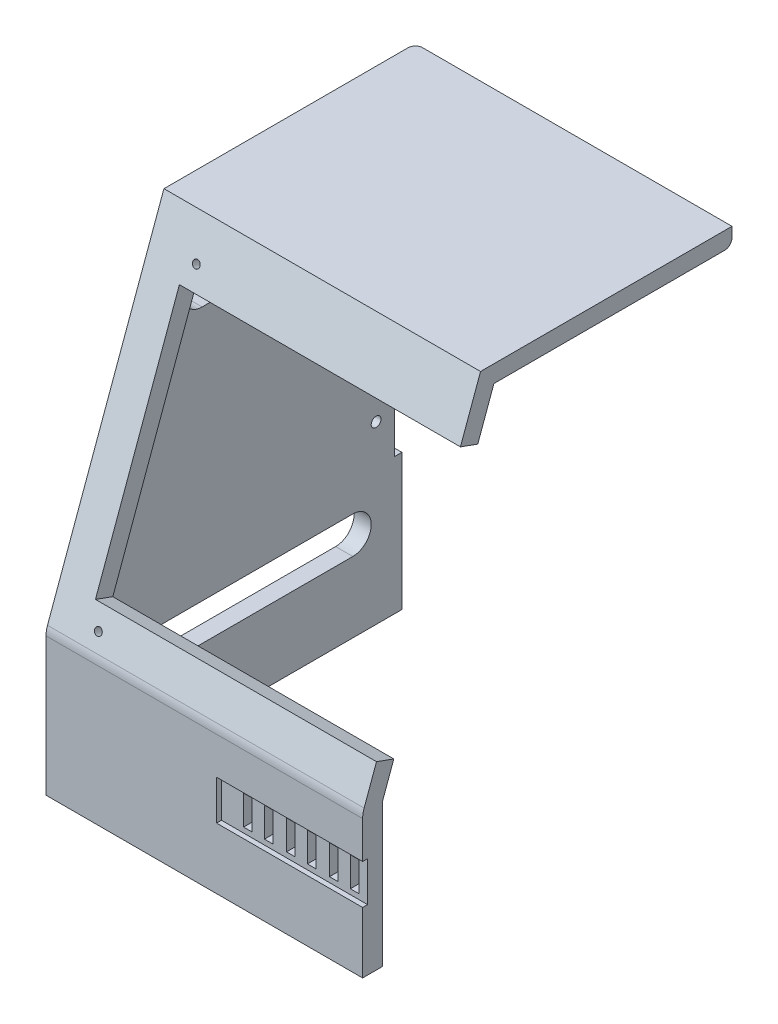
SolidWorks part; units mm, degrees
ref_plane "Front Plane" through (0, 0, 0) normal (0, 0, 1) x (1, 0, 0)
ref_plane "Top Plane" through (0, 0, 0) normal (0, 1, 0) x (1, 0, 0)
ref_plane "Right Plane" through (0, 0, 0) normal (1, 0, 0) x (0, 0, -1)
sketch "Sketch1" plane through (0, 0, 0) normal (0, 0, 1) x (1, 0, 0)
  line L0 (0, 0) -> (170, 0)
  line L1 (170, 0) -> (170, 130)
  line L2 (170, 130) -> (0, 130)
  line L3 (0, 130) -> (0, 0)
  dimension "D1" = 170
  dimension "D2" = 130
extrude "Boss-Extrude1" add sketch "Sketch1" along normal blind 8
sketch "Sketch2" plane through (0, 0, 8) normal (0, 0, 1) x (1, 0, 0)
  line L0 (85, 130) -> (85, 0) construction
  line L1 (170, 130) -> (0, 130) construction
  line L2 (0, 0) -> (170, 0) construction
  line L3 (0, 65) -> (170, 65) construction
  line L4 (0, 130) -> (0, 0) construction
  line L5 (170, 0) -> (170, 130) construction
  line L6 (6.55, 123.35) -> (163.45, 123.35) construction
  line L7 (163.45, 123.35) -> (163.45, 6.65) construction
  line L8 (163.45, 6.65) -> (6.55, 6.65) construction
  line L9 (6.55, 6.65) -> (6.55, 123.35) construction
  line L10 (2.5, 115) -> (167.5, 115)
  line L11 (2.5, 115) -> (2.5, 15)
  line L12 (2.5, 15) -> (167.5, 15)
  line L13 (167.5, 15) -> (167.5, 115)
  circle A0 centre (6.55, 123.35) radius 1.5
  circle A1 centre (163.45, 123.35) radius 1.5
  circle A2 centre (6.55, 6.65) radius 1.5
  circle A3 centre (163.45, 6.65) radius 1.5
  dimension "D3" = 165
  dimension "D1" = 156.9
  dimension "D2" = 116.7
  dimension "D4" = 100
extrude "Cut-Extrude1" cut sketch "Sketch2" against normal blind 21
sketch "Sketch3" plane through (0, 0, 8) normal (0, 0, 1) x (1, 0, 0)
  line L0 (0, 0) -> (170, 0)
  line L1 (170, 0) -> (170, -20)
  line L2 (170, -20) -> (0, -20)
  line L3 (0, -20) -> (0, 0)
extrude "Boss-Extrude2" add sketch "Sketch3" against normal blind 8
sketch "Sketch4" plane through (0, 0, 8) normal (0, 0, 1) x (1, 0, 0)
  line L0 (0, 0) -> (0, -20) construction
  line L1 (0, -10) -> (170, -10) construction
  line L2 (170, -20) -> (170, 130) construction
  line L3 (85, 15) -> (85, -20) construction
  line L4 (2.5, 15) -> (167.5, 15) construction
  line L5 (0, -20) -> (170, -20) construction
  line L6 (52.5, -1.9) -> (52.5, -18.1)
  line L7 (52.5, -1.9) -> (117.5, -1.9)
  line L8 (117.5, -1.9) -> (117.5, -18.1)
  line L9 (117.5, -18.1) -> (52.5, -18.1)
  dimension "D1" = 65
  dimension "D2" = 16.2
extrude "Cut-Extrude2" cut sketch "Sketch4" against normal blind 2
sketch "Sketch5" plane through (0, 0, 6) normal (0, 0, 1) x (1, 0, 0)
  line L0 (52.5, -10) -> (117.5, -10) construction
  line L1 (52.5, -1.9) -> (52.5, -18.1) construction
  line L2 (117.5, -18.1) -> (117.5, -1.9) construction
  line L3 (67.5, -1.9) -> (67.5, -18.1) construction
  line L4 (117.5, -1.9) -> (52.5, -1.9) construction
  line L5 (52.5, -18.1) -> (117.5, -18.1) construction
  line L6 (85, -1.9) -> (85, -18.1) construction
  line L7 (117.5, -1.9) -> (52.5, -1.9) construction
  line L8 (52.5, -18.1) -> (117.5, -18.1) construction
  line L9 (102.5, -1.9) -> (102.5, -18.1) construction
  line L10 (52.5, -1.9) -> (52.5, -18.1) construction
  line L11 (93.75, -1.9) -> (93.75, -18.1) construction
  line L12 (61.5, -4) -> (73.5, -4) construction
  line L13 (73.5, -4) -> (73.5, -16) construction
  line L14 (73.5, -16) -> (61.5, -16) construction
  line L15 (61.5, -16) -> (61.5, -4) construction
  line L16 (96.5, -16) -> (96.5, -4) construction
  line L17 (79, -4) -> (79, -16) construction
  line L18 (79, -16) -> (91, -16) construction
  line L19 (91, -16) -> (91, -4) construction
  line L20 (91, -4) -> (79, -4) construction
  line L21 (108.5, -16) -> (96.5, -16) construction
  line L22 (108.5, -4) -> (108.5, -16) construction
  line L23 (96.5, -4) -> (108.5, -4) construction
  line L24 (61.5, -4) -> (65, -4)
  line L25 (65, -4) -> (65, -16)
  line L26 (65, -16) -> (61.5, -16)
  line L27 (61.5, -16) -> (61.5, -4)
  line L28 (70, -16) -> (73.5, -16)
  line L29 (70, -4) -> (70, -16)
  line L30 (73.5, -4) -> (70, -4)
  line L31 (73.5, -16) -> (73.5, -4)
  line L32 (76.25, -1.9) -> (76.25, -18.1) construction
  line L33 (82.5, -4) -> (82.5, -16)
  line L34 (79, -4) -> (82.5, -4)
  line L35 (79, -16) -> (79, -4)
  line L36 (82.5, -16) -> (79, -16)
  line L37 (87.5, -16) -> (91, -16)
  line L38 (87.5, -4) -> (87.5, -16)
  line L39 (91, -4) -> (87.5, -4)
  line L40 (91, -16) -> (91, -4)
  line L41 (100, -4) -> (100, -16)
  line L42 (96.5, -4) -> (100, -4)
  line L43 (96.5, -16) -> (96.5, -4)
  line L44 (100, -16) -> (96.5, -16)
  line L45 (108.5, -4) -> (105, -4)
  line L46 (108.5, -16) -> (108.5, -4)
  line L47 (105, -16) -> (108.5, -16)
  line L48 (105, -4) -> (105, -16)
  dimension "D1" = 15
  dimension "D2" = 17.5
  dimension "D3" = 17.5
  dimension "D4" = 15
  dimension "D5" = 12
  dimension "D6" = 12
  dimension "D7" = 8.75
  dimension "D8" = 8.75
extrude "Cut-Extrude3" cut sketch "Sketch5" against normal blind 35
sketch "Sketch6" plane through (0, 0, 8) normal (0, 0, 1) x (1, 0, 0)
  line L0 (15.5044, 140) -> (225, 140)
  line L1 (225, 140) -> (225, -35)
  line L2 (225, -35) -> (-10, -35)
  line L3 (-10, -35) -> (-10, 140)
  line L4 (-10, 140) -> (15.5044, 140)
  line L5 (170, 130) -> (0, 130) construction
  line L6 (170, -20) -> (170, 130) construction
  line L7 (0, -20) -> (170, -20) construction
  line L8 (0, 130) -> (170, 130)
  line L9 (170, 130) -> (170, -20)
  line L10 (170, -20) -> (0, -20)
  line L11 (0, -20) -> (0, 130)
  dimension "D1" = 10
  dimension "D2" = 10
  dimension "D3" = 55
  dimension "D4" = 15
extrude "Boss-Extrude3" add sketch "Sketch6" against normal blind 8
sketch "Sketch7" plane through (0, 0, 8) normal (0, 0, 1) x (1, 0, 0)
  line L0 (-10, 140) -> (-17, 140)
  line L1 (-17, 140) -> (-17, -42)
  line L2 (-17, -42) -> (232, -42)
  line L3 (232, -42) -> (232, 140)
  line L4 (232, 140) -> (225, 140)
  line L5 (225, 140) -> (225, -35)
  line L6 (225, -35) -> (-10, -35)
  line L7 (-10, -35) -> (-10, 140)
  dimension "D1" = 7
  dimension "D2" = 7
  dimension "D3" = 7
extrude "Boss-Extrude4" add sketch "Sketch7" against normal blind 138
sketch "Sketch8" plane through (0, -42, 0) normal (0, -1, 0) x (1, 0, 0)
  line L0 (-17, 8) -> (-17, -130)
  line L1 (-17, -130) -> (232, -130)
  line L2 (232, -130) -> (232, 8)
  line L3 (232, 8) -> (-17, 8)
extrude "Boss-Extrude5" add sketch "Sketch8" along normal blind 1
sketch "Sketch9" plane through (232, 0, 0) normal (1, 0, 0) x (0, 0, -1)
  line L0 (75, 140) -> (75, -48) construction
  line L1 (130, 140) -> (-8, 140) construction
  line L3 (-8, -43) -> (-8, 140) construction
  line L4 (-8, 35) -> (130, 35) construction
  line L5 (130, -43) -> (130, 140) construction
  line L6 (38.6, 71.625) -> (111.4, 71.625)
  line L7 (111.4, 71.625) -> (111.4, -1.625)
  line L8 (111.4, -1.625) -> (38.6, -1.625)
  line L9 (38.6, -1.625) -> (38.6, 71.625)
  dimension "D1" = 105
  dimension "D2" = 72.8
  dimension "D3" = 73.25
  dimension "D4" = 75
extrude "Cut-Extrude4" cut sketch "Sketch9" against normal blind 19
sketch "Sketch10" plane through (232, 0, 0) normal (1, 0, 0) x (0, 0, -1)
  line L0 (75, 71.625) -> (75, -1.625) construction
  line L1 (38.6, 35) -> (111.4, 35) construction
  line L2 (111.4, -1.625) -> (111.4, 71.625) construction
  line L3 (38.6, 71.625) -> (38.6, -1.625) construction
  line L4 (111.4, 71.625) -> (38.6, 71.625) construction
  line L5 (38.6, -1.625) -> (111.4, -1.625) construction
  line L6 (36, 74) -> (114, 74) construction
  line L7 (36, 74) -> (36, -4) construction
  line L8 (36, -4) -> (114, -4) construction
  line L9 (114, -4) -> (114, 74) construction
  line L10 (36, 44) -> (36, -4)
  line L11 (36, -4) -> (114, -4)
  line L12 (114, -4) -> (114, 44)
  line L13 (114, 44) -> (119, 44)
  line L14 (119, 44) -> (119, -9)
  line L15 (119, -9) -> (31, -9)
  line L16 (31, -9) -> (31, 44)
  line L17 (31, 44) -> (36, 44)
  dimension "D1" = 78
  dimension "D2" = 78
  dimension "D3" = 5
  dimension "D4" = 5
  dimension "D5" = 5
  dimension "D6" = 30
  dimension "D7" = 30
extrude "Boss-Extrude6" add sketch "Sketch10" along normal blind 5
sketch "Sketch11" plane through (237, 0, 0) normal (1, 0, 0) x (0, 0, -1)
  line L0 (33.5, 44) -> (33.5, -9) construction
  line L1 (36, 44) -> (31, 44) construction
  line L2 (31, -9) -> (119, -9) construction
  line L3 (116.5, 44) -> (116.5, -9) construction
  line L4 (119, 44) -> (114, 44) construction
  circle A0 centre (33.5, 17.5) radius 1.5
  circle A1 centre (116.5, 17.5) radius 1.5
extrude "Cut-Extrude5" cut sketch "Sketch11" against normal blind 56
sketch "Sketch12" plane through (0, -35, 0) normal (0, 1, 0) x (1, 0, 0)
  line L0 (107.5, 130) -> (107.5, 0) construction
  line L1 (225, 130) -> (-10, 130) construction
  line L2 (-10, 0) -> (225, 0) construction
  line L3 (107.5, 65) -> (225, 65) construction
  line L4 (153.75, 107) -> (153.75, 83) construction
  line L5 (225, 130) -> (225, 0) construction
  line L6 (166.25, 65) -> (166.25, 0) construction
  line L7 (225, 0) -> (-10, 0) construction
  line L8 (166.25, 65) -> (166.25, 130) construction
  line L9 (153.75, 107) -> (178.75, 107) construction
  line L10 (153.75, 83) -> (178.75, 83) construction
  line L11 (178.75, 83) -> (178.75, 107) construction
  line L12 (155.75, 107) -> (155.75, 83) construction
  line L13 (176.75, 107) -> (176.75, 83) construction
  line L14 (153.75, 97.5) -> (178.75, 97.5) construction
  line L15 (153.75, 85) -> (178.75, 85) construction
  line L16 (187.25, 130) -> (187.25, 65) construction
  line L17 (145.25, 130) -> (145.25, 65) construction
  circle A0 centre (166.25, 32.5) radius 9
  circle A1 centre (166.25, 97.5) radius 6.5
  circle A2 centre (155.75, 97.5) radius 1
  circle A3 centre (155.75, 85) radius 1
  circle A4 centre (176.75, 85) radius 1
  circle A5 centre (176.75, 97.5) radius 1
  circle A6 centre (145.25, 97.5) radius 2.75
  circle A7 centre (187.25, 97.5) radius 2.75
  dimension "D1" = 18
  dimension "D2" = 25
  dimension "D4" = 13
  dimension "D7" = 21
  dimension "D8" = 24
  dimension "D3" = 9.5
  dimension "D5" = 2
  dimension "D6" = 12.5
extrude "Cut-Extrude6" cut sketch "Sketch12" against normal blind 115
sketch "Sketch13" plane through (0, -43, 0) normal (0, -1, 0) x (1, 0, 0)
  line L0 (107.5, 8) -> (107.5, -130) construction
  line L1 (232, 8) -> (-17, 8) construction
  line L2 (-17, -130) -> (232, -130) construction
  line L3 (107.5, -61) -> (232, -61) construction
  line L4 (232, -130) -> (232, 8) construction
  line L5 (166.25, -97.5) -> (166.25, -61) construction
  line L6 (136.9548, -61) -> (136.9548, -130) construction
  line L7 (195.5452, -61) -> (195.5452, -130) construction
  line L8 (136.9548, -78.4497) -> (195.5452, -78.4497) construction
  line L9 (136.9548, -108.5255) -> (195.5452, -108.5255) construction
  line L10 (136.9548, -78.4497) -> (195.5452, -78.4497)
  line L11 (195.5452, -78.4497) -> (195.5452, -108.5255)
  line L12 (195.5452, -108.5255) -> (136.9548, -108.5255)
  line L13 (136.9548, -108.5255) -> (136.9548, -78.4497)
  dimension "D1" = 124.5
  dimension "D2" = 124.5
extrude "Cut-Extrude7" cut sketch "Sketch13" against normal blind 3
fillet "Fillet1" radius 2 4 edges at (136.9548, -40, -93.4876) (166.25, -40, -108.5255) (195.5452, -40, -93.4876) (166.25, -40, -78.4497)
sketch "Sketch15" plane through (0, 140, 0) normal (0, 1, 0) x (1, 0, 0)
  line L0 (-17, -4) -> (232, -4) construction
  line L1 (-17, 130) -> (-17, -8) construction
  line L2 (232, 130) -> (232, -8) construction
  line L3 (232, -8) -> (-17, -8) construction
  circle A0 centre (5, -4) radius 1.5
  circle A1 centre (20, -4) radius 1.5
  circle A2 centre (217, -4) radius 1.5
  circle A3 centre (202, -4) radius 1.5
  dimension "D2" = 15
  dimension "D1" = 4
  dimension "D3" = 15
  dimension "D4" = 15
  dimension "D5" = 15
extrude "Cut-Extrude8" cut sketch "Sketch15" against normal blind 10
ref_plane "Plane3" through (0, 1.7547, 4.8209) normal (0, 0.342, 0.9397) x (1, 0, 0)
sketch "Sketch18" plane through (232, 0, 0) normal (1, 0, 0) x (0, 0, -1)
  line L0 (45.4963, 140) -> (-8, 140)
  line L1 (130, 140) -> (-8, 140) construction
  line L2 (42.0188, 130.4456) -> (-51.6606, -126.9362) construction
  line L3 (-8, 140) -> (-8, 15)
  line L4 (-8, 15) -> (0, 15)
  line L5 (0, 15) -> (-8, 15) construction
  line L6 (0, 15) -> (45.4963, 140)
extrude "Cut-Extrude10" cut sketch "Sketch18" against normal blind 261
sketch "Sketch19" plane through (0, 0, 8) normal (0, 0, 1) x (1, 0, 0)
  circle A0 centre (6.55, 6.65) radius 1.5
  circle A1 centre (163.45, 6.65) radius 1.5
extrude "Boss-Extrude7" add sketch "Sketch19" against normal up to surface (8 mm away) up to face at (63.25, -10, 0)
ref_plane "Plane4" through (107.5, 0, 0) normal (1, 0, 0) x (0, 0, -1)
sketch "Sketch21" plane through (107.5, 0, 0) normal (1, 0, 0) x (0, 0, -1)
  line L0 (45.4963, 140) -> (0, 15)
  line L1 (42.0188, 130.4456) -> (-51.6606, -126.9362) construction
  line L2 (130, 140) -> (45.4963, 140) construction
  line L3 (0, 15) -> (-8, 15)
  line L4 (-8, 15) -> (37.4963, 140)
  line L5 (37.4963, 140) -> (45.4963, 140)
  dimension "D1" = 8
  dimension "D2" = 8
extrude "Boss-Extrude12" add sketch "Sketch21" along normal up to surface (124.5 mm away) and the other way up to surface (124.5 mm away) up to face at (232, 37.3333, -48.2494) other way up to face at (-17, 37.3333, -48.2494)
sketch "Sketch22" plane through (0, 4.3258, 11.8851) normal (0, 0.342, 0.9397) x (1, 0, 0)
  line L0 (177, 144.3814) -> (177, 11.3592) construction
  line L1 (232, 144.3814) -> (-17, 144.3814) construction
  line L2 (-17, 11.3592) -> (232, 11.3592) construction
  line L3 (232, 144.3814) -> (232, 11.3592) construction
  line L4 (177, 77.8703) -> (-17, 77.8703) construction
  line L5 (-17, 144.3814) -> (-17, 11.3592) construction
  line L6 (80, 77.8703) -> (80, 11.3592) construction
  line L7 (80, 77.8703) -> (80, 144.3814) construction
  line L8 (1.55, 136.2203) -> (158.45, 136.2203) construction
  line L9 (158.45, 136.2203) -> (158.45, 19.5203) construction
  line L10 (158.45, 19.5203) -> (1.55, 19.5203) construction
  line L11 (1.55, 19.5203) -> (1.55, 136.2203) construction
  line L12 (-2.5, 127.8703) -> (-2.5, 27.8703)
  line L13 (-2.5, 27.8703) -> (162.5, 27.8703)
  line L14 (162.5, 27.8703) -> (162.5, 127.8703)
  line L15 (162.5, 127.8703) -> (-2.5, 127.8703)
  circle A0 centre (1.55, 136.2203) radius 1.5
  circle A1 centre (158.45, 136.2203) radius 1.5
  circle A2 centre (1.55, 19.5203) radius 1.5
  circle A3 centre (158.45, 19.5203) radius 1.5
  dimension "D5" = 100
  dimension "D1" = 55
  dimension "D2" = 133.0222
  dimension "D3" = 116.7
  dimension "D4" = 156.9
  dimension "D6" = 165
extrude "Cut-Extrude11" cut sketch "Sketch22" against normal blind 18
fillet "Fillet2" radius 10 1 edges at (107.5, 15, 8)
sketch "Sketch24" plane through (-10, 0, 0) normal (1, 0, 0) x (0, 0, -1)
  line L0 (130, 48.5) -> (12.193, 48.5) construction
  line L1 (130, -43) -> (130, 140) construction
  line L2 (45.4963, 140) -> (0, 15) construction
  line L3 (108, 83.5) -> (108, 13.5) construction
  line L4 (108, 83.5) -> (130, 83.5) construction
  line L5 (108, 13.5) -> (130, 13.5) construction
  line L6 (130, 13.5) -> (130, 83.5) construction
  line L7 (108, 28.5) -> (130, 28.5) construction
  line L8 (108, 68.5) -> (130, 68.5) construction
  line L9 (113.5, 13.5) -> (113.5, 83.5) construction
  line L10 (119.5, 83.5) -> (119.5, 13.5) construction
  line L11 (130, 84.5) -> (127, 84.5)
  line L12 (127, 84.5) -> (127, 12.5)
  line L13 (127, 12.5) -> (130, 12.5)
  line L14 (130, 12.5) -> (130, 84.5)
  circle A0 centre (113.5, 48.5) radius 2
  circle A1 centre (119.5, 68.5) radius 2
  circle A2 centre (119.5, 28.5) radius 2
  dimension "D7" = 72
  dimension "D1" = 70
  dimension "D2" = 22
  dimension "D3" = 15
  dimension "D4" = 20
  dimension "D5" = 5.5
  dimension "D6" = 11.5
extrude "Cut-Extrude15" cut sketch "Sketch24" against normal blind 42
sketch "Sketch25" plane through (232, 0, 0) normal (1, 0, 0) x (0, 0, -1)
  line L0 (45.4963, 140) -> (130, 140)
  line L1 (130, 140) -> (130, -43)
  line L2 (130, -43) -> (0, -43)
  line L3 (130, -43) -> (-8, -43) construction
  line L4 (0, -43) -> (0, 15)
  line L5 (0, 15) -> (45.4963, 140)
extrude "Cut-Extrude16" cut sketch "Sketch25" against normal up to surface (242 mm away) and the other way blind 140 up to face at (-10, 50.5, -113.5)
sketch "Sketch27" plane through (0, 140, 0) normal (0, 1, 0) x (1, 0, 0)
  line L0 (232, 37.4963) -> (232, 142.4963)
  line L1 (232, 142.4963) -> (-17, 142.4963)
  line L2 (-17, 142.4963) -> (-17, 37.4963)
  line L3 (-17, 37.4963) -> (232, 37.4963)
extrude "Boss-Extrude13" add sketch "Sketch27" along normal blind 7
sketch "Sketch28" plane through (232, 0, 0) normal (1, 0, 0) x (0, 0, -1)
  line L0 (37.4963, 140) -> (40.0441, 147)
  line L1 (37.4963, 147) -> (142.4963, 147) construction
  line L2 (0, 15) -> (45.4963, 140) construction
  line L3 (40.0441, 147) -> (37.4963, 147)
  line L4 (37.4963, 147) -> (37.4963, 140)
extrude "Cut-Extrude17" cut sketch "Sketch28" against normal up to surface (249 mm away) up to face at (-17, 46.5, -113.5)
fillet "Fillet6" radius 3 1 edges at (107.5, 140, -142.4963)
fillet "Fillet7" radius 3 3 edges at (-17, 145, -142.4963) (-17, 140.8787, -141.6176) (-17, 140, -134.7481)
sketch "Sketch29" plane through (232, 0, 0) normal (1, 0, 0) x (0, 0, -1)
  line L0 (-8, -43) -> (0, -43)
  line L1 (0, -43) -> (0, 15)
  line L2 (0, 15) -> (45.4963, 140)
  line L3 (45.4963, 140) -> (139.4963, 140)
  line L4 (142.8768, 143.3805) -> (142.4963, 147)
  line L5 (142.4963, 147) -> (40.0441, 147)
  line L6 (40.0441, 147) -> (-7.3969, 16.6569)
  line L7 (-8, 13.2367) -> (-8, -43)
  arc A0 (139.4963, 140) -> (142.8768, 143.3805) centre (139.4963, 143.3805) ccw
  arc A1 (-7.3969, 16.6569) -> (-8, 13.2367) centre (2, 13.2367) ccw
extrude "Boss-Extrude14" add sketch "Sketch29" along normal blind 9
sketch "Sketch30" plane through (0, 147, 0) normal (0, 1, 0) x (1, 0, 0)
  line L0 (241, 140.8768) -> (241, 132.8768) construction
  line L1 (203.25, 142.4963) -> (203.25, 129.9214) construction
  line L2 (241, 136.8768) -> (104.3928, 136.8768) construction
  line L3 (233.25, 142.4963) -> (233.25, 132.8768) construction
  line L4 (218.25, 142.4963) -> (218.25, 129.9214) construction
  line L5 (232, 142.4963) -> (-14, 142.4963) construction
  circle A0 centre (218.25, 136.8768) radius 1.5
  circle A1 centre (203.25, 136.8768) radius 1.5
  dimension "D1" = 2
  dimension "D2" = 8
  dimension "D3" = 7.75
  dimension "D4" = 15
  dimension "D5" = 1.6195
  dimension "D6" = 15
extrude "Cut-Extrude18" cut sketch "Sketch30" against normal blind 10
sketch "Sketch31" plane through (0, 0, 8) normal (0, 0, 1) x (1, 0, 0)
  line L0 (241, -43) -> (241, -35) construction
  line L1 (241, 13.2367) -> (241, -43) construction
  line L2 (241, -39) -> (190.9905, -39) construction
  line L3 (234, -35) -> (234, -43) construction
  line L4 (241, -43) -> (-17, -43) construction
  line L5 (219, -35) -> (219, -43) construction
  line L6 (204, -35) -> (204, -43) construction
  circle A0 centre (219, -39) radius 1.5
  circle A1 centre (204, -39) radius 1.5
  dimension "D1" = 7
  dimension "D2" = 15
  dimension "D3" = 15
extrude "Cut-Extrude19" cut sketch "Sketch31" against normal blind 49
sketch "Sketch32" plane through (-17, 0, 0) normal (-1, 0, 0) x (0, 0, 1)
  line L0 (-110, -6.7633) -> (-12, -6.7633) construction
  line L1 (-110, -6.7633) -> (-12, -6.7633) construction
  line L2 (-110, 0.7367) -> (-12, 0.7367)
  line L3 (-110, -14.2633) -> (-12, -14.2633)
  line L4 (-130, 12.5) -> (-130, -43) construction
  line L5 (8, 13.2367) -> (8, -43) construction
  line L6 (-110, 112) -> (-48.5887, 112) construction
  line L7 (-110, 112) -> (-48.5887, 112) construction
  line L8 (-110, 119.5) -> (-48.5887, 119.5)
  line L9 (-110, 104.5) -> (-48.5887, 104.5)
  line L10 (-130, 143) -> (-130, 84.5) construction
  line L11 (-40.0441, 147) -> (7.3969, 16.6569) construction
  line L12 (-139.4963, 147) -> (-40.0441, 147) construction
  arc A0 (-110, 0.7367) -> (-110, -14.2633) centre (-110, -6.7633) ccw
  arc A1 (-12, -14.2633) -> (-12, 0.7367) centre (-12, -6.7633) ccw
  arc A2 (8, 13.2367) -> (7.3969, 16.6569) centre (-2, 13.2367) ccw construction
  arc A3 (-110, 119.5) -> (-110, 104.5) centre (-110, 112) ccw
  arc A4 (-48.5887, 104.5) -> (-48.5887, 119.5) centre (-48.5887, 112) ccw
  point P3 (-61, -6.7633)
  point P18 (-79.2943, 112)
  dimension "D1" = 20
  dimension "D2" = 20
  dimension "D3" = 15
  dimension "D4" = 20
  dimension "D5" = 20
  dimension "D6" = 20
  dimension "D7" = 35
  dimension "D8" = 15
extrude "Cut-Extrude20" cut sketch "Sketch32" against normal blind 49
sketch "Sketch33" plane through (0, 0, 8) normal (0, 0, 1) x (1, 0, 0)
  line L0 (112, -43) -> (112, 147) construction
  line L1 (241, -43) -> (-17, -43) construction
  line L2 (-17, 147) -> (241, 147) construction
  line L3 (112, -43) -> (112, 147)
  line L4 (112, 147) -> (241, 147)
  line L5 (241, 147) -> (241, -43)
  line L6 (241, -43) -> (112, -43)
extrude "Cut-Extrude21" cut sketch "Sketch33" against normal blind 200
